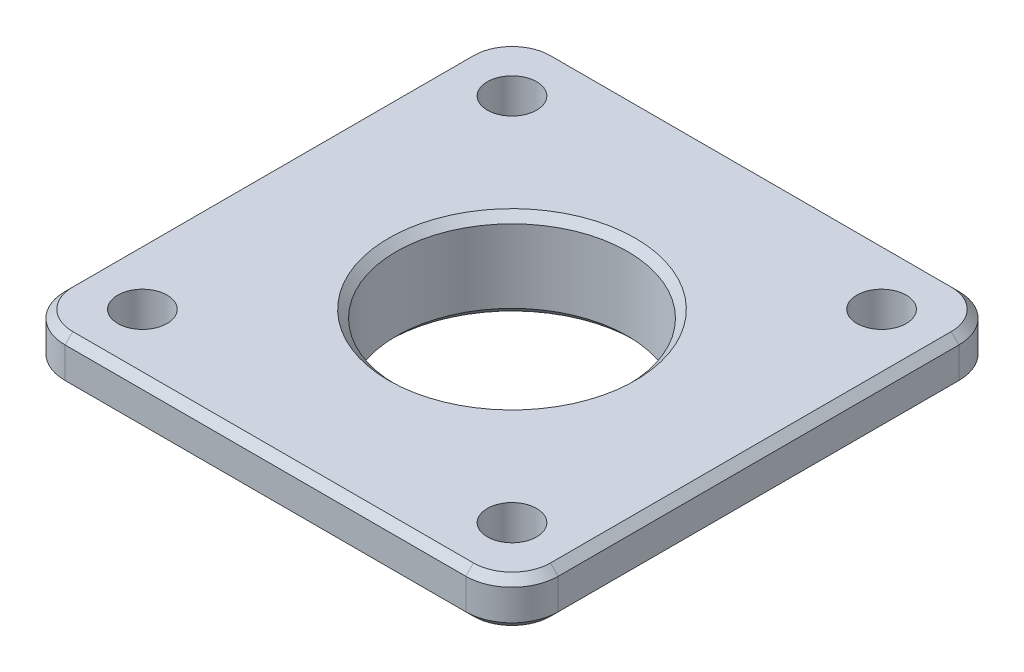
SolidWorks part; units mm, degrees
ref_plane "Ebene vorne" through (0, 0, 0) normal (0, 0, 1) x (1, 0, 0)
ref_plane "Ebene oben" through (0, 0, 0) normal (0, 1, 0) x (1, 0, 0)
ref_plane "Ebene rechts" through (0, 0, 0) normal (1, 0, 0) x (0, 0, -1)
ref_axis "Achse1" through (0, -0.15, 0) along (0, 1, 0)
sketch "Skizze1" plane through (0, 0, 0) normal (0, 1, 0) x (1, 0, 0)
  line L0 (0, 89.8376) -> (0, -75.8682) construction
  line L1 (-94.5744, 0) -> (87.0277, 0) construction
  line L2 (-16, -13) -> (-16, 13)
  line L3 (-13, 16) -> (13, 16)
  line L4 (16, -13) -> (16, 13)
  line L5 (-13, -16) -> (13, -16)
  line L6 (0, 0) -> (-24.6771, 24.6771) construction
  arc A0 (-13, 16) -> (-16, 13) centre (-13, 13) ccw
  arc A1 (13, 16) -> (16, 13) centre (13, 13) cw
  arc A2 (13, -16) -> (16, -13) centre (13, -13) ccw
  arc A3 (-13, -16) -> (-16, -13) centre (-13, -13) cw
  circle A4 centre (0, 0) radius 7.5
  circle A5 centre (0, 0) radius 16.955 construction
  circle A6 centre (-11.989, 11.989) radius 1.6
  circle A7 centre (11.989, 11.989) radius 1.6
  circle A8 centre (11.989, -11.989) radius 1.6
  circle A9 centre (-11.989, -11.989) radius 1.6
  point P7 (-16, 0)
  point P13 (0, 16)
  point P20 (0, -16)
  point P21 (16, 0)
  dimension "D1" = 3
  dimension "D4" = 15
  dimension "D6" = 3.2
  dimension "D7" = 33.91
  dimension "D2" = 32
  dimension "D3" = 32
  dimension "D5" = 45
extrude "Aufsatz-Linear austragen1" add sketch "Skizze1" along normal blind 3
sketch "Skizze2" plane through (0, 0, 0) normal (0, -1, 0) x (1, 0, 0)
  circle A0 centre (0, 0) radius 12.3
  circle A1 centre (0, 0) radius 7.5
  circle A2 centre (0, 0) radius 7.5 construction
  dimension "D1" = 24.6
extrude "Aufsatz-Linear austragen2" add sketch "Skizze2" along normal blind 2.75
chamfer "Fase1" distance 0.5 angle 45 19 edges at (16, 0, 0) (15.1213, 0, -15.1213) (15.1213, 0, 15.1213) (0, 0, -16) (0, 0, 16) (-15.1213, 0, -15.1213) (-15.1213, 0, 15.1213) (-16, 0, 0) (16, 3, 0) (15.1213, 3, -15.1213) (15.1213, 3, 15.1213) (0, 3, -16) (0, 3, 16) (-15.1213, 3, -15.1213) (-15.1213, 3, 15.1213) (-16, 3, 0) (0, 3, 7.5) (0, -2.75, -7.5) (0, -2.75, -12.3)
